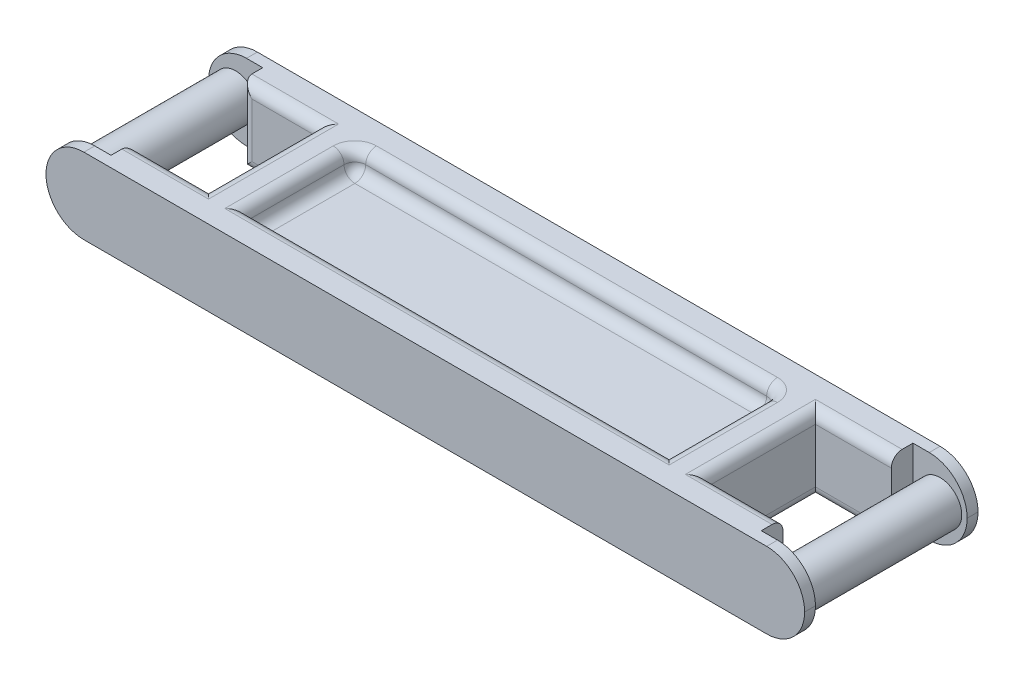
SolidWorks part; units mm, degrees
material "Rubber"
ref_plane "Front Plane" through (0, 0, 0) normal (0, 0, 1) x (1, 0, 0)
ref_plane "Top Plane" through (0, 0, 0) normal (0, 1, 0) x (1, 0, 0)
ref_plane "Right Plane" through (0, 0, 0) normal (1, 0, 0) x (0, 0, -1)
sketch "Sketch1" plane through (0, 0, 0) normal (0, 1, 0) x (1, 0, 0)
  line L1 (-35, 8) -> (35, 8)
  line L2 (-35, 8) -> (-35, -8)
  line L3 (-35, -8) -> (35, -8)
  line L4 (35, 8) -> (35, -8)
  line L5 (-35, 8) -> (35, -8) construction
  line L6 (-35, -8) -> (35, 8) construction
  point P0 (0, 0)
extrude "Boss-Extrude1" add sketch "Sketch1" along normal blind 7
sketch "Sketch2" plane through (0, 7, 0) normal (0, 1, 0) x (1, 0, 0)
  line L0 (-35, 8) -> (-35, 7)
  line L1 (-35, 8) -> (-35, -8) construction
  line L2 (-35, 7) -> (-30, 7)
  line L3 (-30, 7) -> (-30, 5)
  line L4 (-30, 5) -> (-23, 5)
  line L5 (-3.85, 0) -> (3.85, 0) construction
  line L6 (-35, -7) -> (-30, -7)
  line L7 (-30, -7) -> (-30, -5)
  line L8 (-30, -5) -> (-23, -5)
  line L9 (-23, 5) -> (-23, -5)
  line L10 (-35, 7) -> (-35, -7)
  line L11 (0, -3.85) -> (0, 3.85) construction
  line L12 (30, -7) -> (30, -5)
  line L13 (35, -7) -> (30, -7)
  line L14 (30, -5) -> (23, -5)
  line L15 (23, 5) -> (23, -5)
  line L16 (30, 7) -> (30, 5)
  line L17 (35, 7) -> (30, 7)
  line L18 (30, 5) -> (23, 5)
  line L19 (35, 7) -> (35, -7)
  line M9 (35, -8) -> (35, 8)
  line M11 (-35, 8) -> (-35, -8)
extrude "Cut-Extrude1" cut sketch "Sketch2" against normal blind 17 contours L9 L4 L3 L2 L6 L7 L8 M11 | L16 L18 L15 L14 L12 L13 L17 M9
sketch "Sketch3" plane through (0, 0, -7) normal (0, 0, 1) x (1, 0, 0)
  line L0 (0, -3.85) -> (0, 3.85) construction
  circle A0 centre (-32.5, 3.5) radius 2
  circle A1 centre (32.5, 3.5) radius 2
extrude "Boss-Extrude2" add sketch "Sketch3" along normal up to surface (14 mm away) up to face at (-32.5, 3.5, 7)
sketch "Sketch4" plane through (0, 7, 0) normal (0, 1, 0) x (1, 0, 0)
  line L1 (-19.5, 5) -> (19.5, 5)
  line L2 (-19.5, 5) -> (-19.5, -5)
  line L3 (-19.5, -5) -> (19.5, -5)
  line L4 (19.5, 5) -> (19.5, -5)
  line L5 (-19.5, 5) -> (19.5, -5) construction
  line L6 (-19.5, -5) -> (19.5, 5) construction
  point P0 (0, 0)
extrude "Cut-Extrude2" cut sketch "Sketch4" against normal blind 2
ref_plane "Plane1" through (0, 3.5, 0) normal (0, 1, 0) x (1, 0, 0)
mirror "Mirror1" about plane through (0, 3.5, 0) normal (0, 1, 0) of "Cut-Extrude2"
fillet "Fillet1" radius 1 30 edges at (19.5, 7, 0) (0, 5, 5) (-19.5, 5, 0) (19.5, 5, 0) (0, 5, -5) (0, 7, -5) (-26.5, 7, -5) (-26.5, 0, -5) (-26.5, 0, 5) (-26.5, 7, 5) (-30, 3.5, 5) (-30, 3.5, -5) (-23, 0, 0) (-23, 7, 0) (26.5, 0, 5) (26.5, 7, 5) (26.5, 0, -5) (26.5, 7, -5) (23, 0, 0) (23, 7, 0) (19.5, 0, 0) (19.5, 2, 0) (0, 0, -5) (0, 2, -5) (0, 2, 5) (0, 0, 5) (-19.5, 0, 0) (-19.5, 2, 0) (0, 7, 5) (-19.5, 7, 0)
fillet "Fillet2" radius 3.5 8 edges at (-35, 7, 7.5) (-35, 0, 7.5) (-35, 0, -7.5) (-35, 7, -7.5) (35, 0, -7.5) (35, 7, -7.5) (35, 0, 7.5) (35, 7, 7.5)
